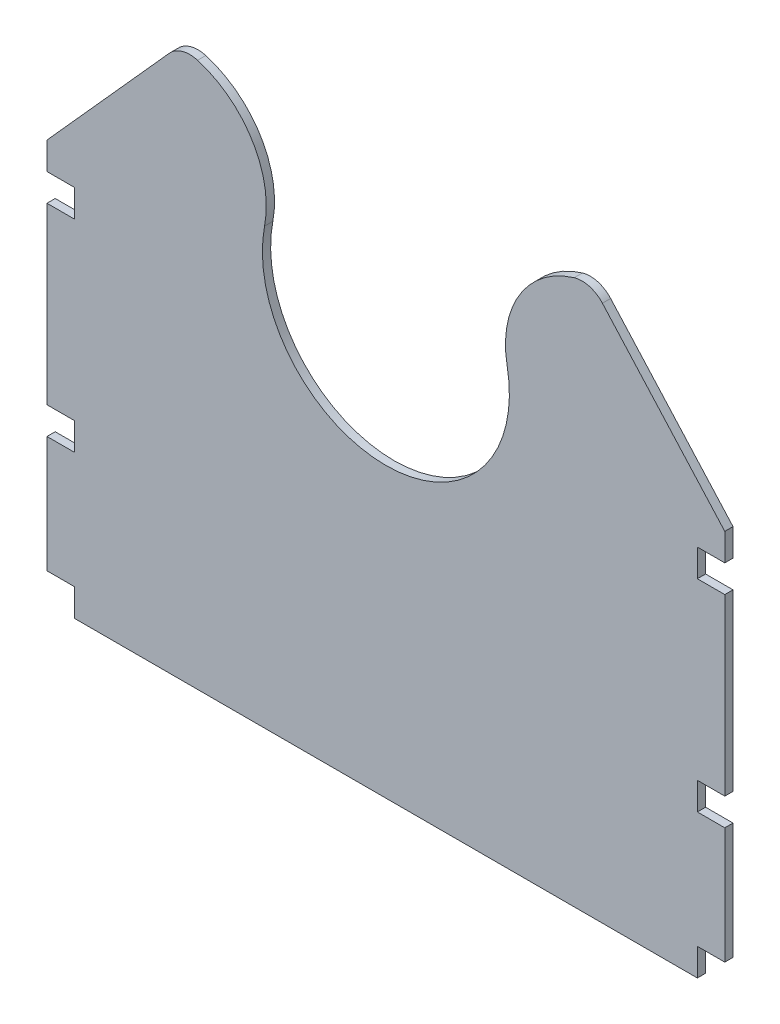
SolidWorks part; units mm, degrees
ref_plane "Plan de face" through (0, 0, 0) normal (0, 0, 1) x (1, 0, 0)
ref_plane "Plan de dessus" through (0, 0, 0) normal (0, 1, 0) x (1, 0, 0)
ref_plane "Plan de droite" through (0, 0, 0) normal (1, 0, 0) x (0, 0, -1)
sketch "Esquisse1" plane through (0, 0, 0) normal (0, 0, 1) x (1, 0, 0)
  line L0 (0, 0) -> (280.2, 0) construction
  line L1 (280.2, 0) -> (280.2, 127.45) construction
  line L2 (280.2, 127.45) -> (215.1, 200) construction
  line L3 (215.1, 200) -> (65.1, 200) construction
  line L4 (65.1, 200) -> (0, 127.45) construction
  line L5 (0, 0) -> (0, 127.45) construction
  line L6 (0, 0) -> (0, 127.45)
  line L7 (0, 127.45) -> (65.1, 200)
  line L8 (65.1, 200) -> (215.1, 200)
  line L9 (215.1, 200) -> (280.2, 127.45)
  line L10 (280.2, 127.45) -> (280.2, 0)
  line L11 (280.2, 0) -> (0, 0)
  point P3 (140.1, 200)
  point P8 (140.1, 0)
  dimension "D1" = 280.2
  dimension "D2" = 200
  dimension "D3" = 127.45
  dimension "D4" = 127.45
  dimension "D5" = 150
extrude "Boss.-Extru.1" add sketch "Esquisse1" along normal blind 3
sketch "Esquisse2" plane through (0, 0, 0) normal (0, 0, -1) x (-1, 0, 0)
  line L1 (-16.6, 252) -> (-16.6, 0) construction
  line L2 (-16.6, 0) -> (-16.6, 145.9694)
  line L3 (-16.6, 0) -> (0, 0)
  line L4 (0, 0) -> (0, 127.45)
  line L5 (0, 127.45) -> (-16.6, 145.9694)
  line L6 (-140.1, 200) -> (-140.1, -18.7191) construction
  line L7 (-215.1, 200) -> (-65.1, 200) construction
  line L8 (-280.2, 127.45) -> (-263.6, 145.9694)
  line L9 (-280.2, 0) -> (-280.2, 127.45)
  line L10 (-263.6, 0) -> (-280.2, 0)
  line L11 (-263.6, 0) -> (-263.6, 145.9694)
extrude "Enlèv. mat.-Extru.1" cut sketch "Esquisse2" against normal through all
sketch "Esquisse4" plane through (0, 0, 3) normal (0, 0, 1) x (1, 0, 0)
  line L0 (140.1, 200) -> (140.1, -14.9568) construction
  line L1 (215.1, 200) -> (65.1, 200) construction
  line L2 (16.6, 145.9497) -> (16.6, 0) construction
  line L3 (16.6, 0) -> (26.6, 0)
  line L4 (16.6, 0) -> (16.6, 10)
  line L5 (16.6, 10) -> (26.6, 10)
  line L6 (26.6, 0) -> (26.6, 10)
  line L7 (16.6, 52.4) -> (26.6, 52.4)
  line L8 (16.6, 52.4) -> (16.6, 62.4)
  line L9 (16.6, 62.4) -> (26.6, 62.4)
  line L10 (26.6, 52.4) -> (26.6, 62.4)
  line L11 (253.6, 126) -> (253.6, 136)
  line L12 (16.6, 126) -> (26.6, 126)
  line L13 (16.6, 126) -> (16.6, 136)
  line L14 (16.6, 136) -> (26.6, 136)
  line L15 (26.6, 126) -> (26.6, 136)
  line L16 (263.6, 136) -> (253.6, 136)
  line L17 (263.6, 126) -> (263.6, 136)
  line L18 (263.6, 126) -> (253.6, 126)
  line L19 (253.6, 52.4) -> (253.6, 62.4)
  line L20 (263.6, 62.4) -> (253.6, 62.4)
  line L21 (263.6, 52.4) -> (263.6, 62.4)
  line L22 (263.6, 52.4) -> (253.6, 52.4)
  line L23 (253.6, 0) -> (253.6, 10)
  line L24 (263.6, 10) -> (253.6, 10)
  line L25 (263.6, 0) -> (263.6, 10)
  line L26 (263.6, 0) -> (253.6, 0)
  point P19 (21.6, 62.4)
  dimension "D1" = 10
  dimension "D2" = 10
  dimension "D3" = 10
  dimension "D4" = 10
  dimension "D5" = 10
  dimension "D6" = 10
  dimension "D7" = 42.4
  dimension "D8" = 63.6
extrude "Enlèv. mat.-Extru.2" cut sketch "Esquisse4" against normal through all
sketch "Esquisse5" plane through (0, 0, 3) normal (0, 0, 1) x (1, 0, 0)
  line L0 (218.6812, 200) -> (140.1, 200)
  line L1 (215.1, 200) -> (65.1, 200) construction
  line L2 (140.1, 200) -> (140.1, 150) construction
  line L3 (61.5188, 200) -> (218.6812, 200)
  arc A0 (95.8981, 158.4375) -> (184.3019, 158.4375) centre (140.1, 150) ccw
  arc A1 (95.8981, 158.4375) -> (61.5188, 200) centre (61.5188, 165) ccw
  arc A2 (184.3019, 158.4375) -> (218.6812, 200) centre (218.6812, 165) cw
  point P7 (140.1, 200)
  line M26 (215.1, 200) -> (65.1, 200)
  dimension "D1" = 90
  dimension "D3" = 70
  dimension "D2" = 50
extrude "Enlèv. mat.-Extru.3" cut sketch "Esquisse5" against normal through all contours A0 A2 A1 M26 region at (140.1, 158.7154, 3)
fillet "Congé2" radius 10 2 edges at (64.9488, 199.8315, 1.5) (215.2512, 199.8315, 1.5)
